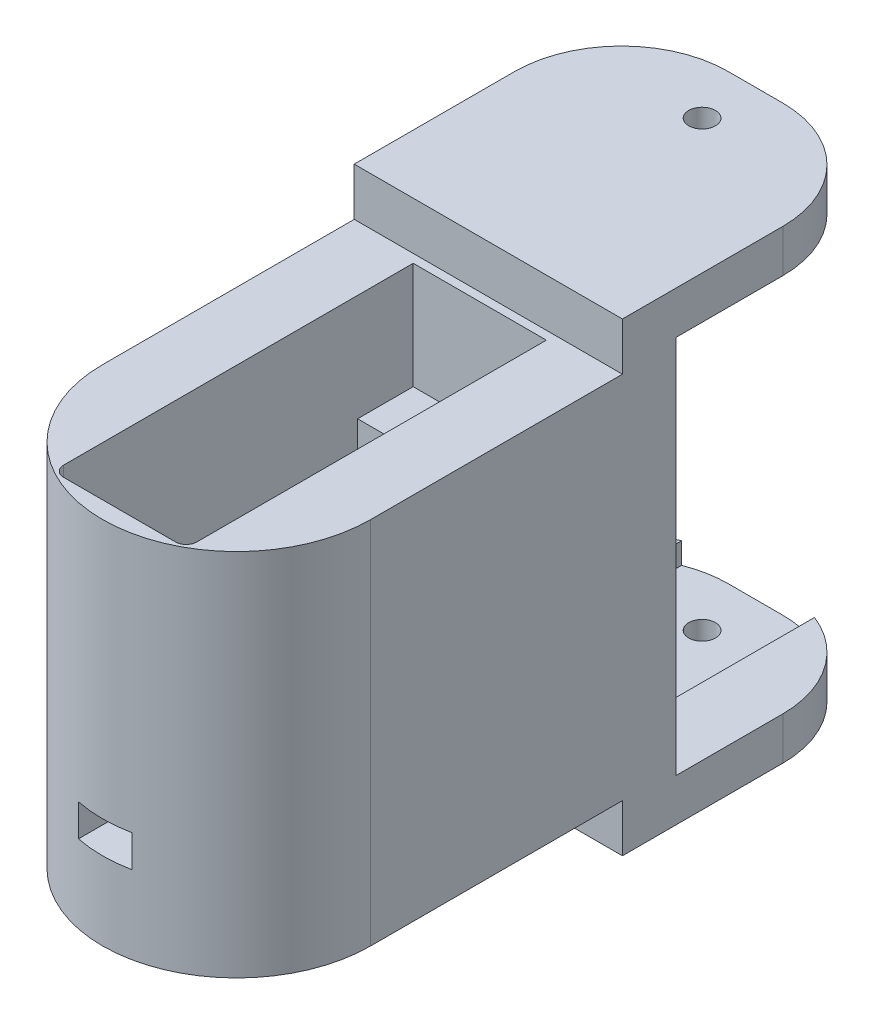
SolidWorks part; units mm, degrees
ref_plane "Front Plane" through (0, 0, 0) normal (0, 0, 1) x (1, 0, 0)
ref_plane "Top Plane" through (0, 0, 0) normal (0, 1, 0) x (1, 0, 0)
ref_plane "Right Plane" through (0, 0, 0) normal (1, 0, 0) x (0, 0, -1)
sketch "Sketch4" plane through (0, 0, 0) normal (0, 0, 1) x (1, 0, 0)
  line L1 (-6.23, -9.975) -> (6.23, -9.975)
  line L2 (-6.23, -9.975) -> (-6.23, 7.275)
  line L3 (-6.23, 7.275) -> (6.23, 7.275)
  line L4 (6.23, -9.975) -> (6.23, 7.275)
  point P4 (0, 7.275)
  dimension "D1" = 12.46
  dimension "D2" = 17.25
  dimension "D3" = 9.975
extrude "Boss-Extrude3" add sketch "Sketch4" along normal blind 6
sketch "Sketch8" plane through (0, -9.975, 0) normal (0, -1, 0) x (-1, 0, 0)
  circle A0 centre (0, -23.55) radius 12.5468
  circle A1 centre (0, -23.55) radius 11.15
  dimension "D1" = 22.3
  dimension "D2" = 23.55
extrude "Boss-Extrude6" add sketch "Sketch8" along normal blind 7.3 and the other way up to surface (17.25 mm away) other way up to face at (0, 7.275, 3)
sketch "Sketch5" plane through (0, 7.275, 0) normal (0, 1, 0) x (1, 0, 0)
  line L8 (12.5468, -23.55) -> (12.5468, 0)
  line L9 (12.5468, 0) -> (6.23, 0)
  line L10 (-12.5468, -23.55) -> (-12.5468, 0)
  line L11 (-12.5468, 0) -> (-6.23, 0)
  line L12 (-6.23, 0) -> (-6.23, -29.7)
  line L14 (6.23, -29.7) -> (6.23, 0)
  line L15 (-6.23, -29.7) -> (6.23, -29.7)
  line L16 (6.23, -6) -> (-6.23, -6) construction
  circle A0 centre (0, -23.55) radius 12.5468 construction
  arc A1 (-12.5468, -23.55) -> (12.5468, -23.55) centre (0, -23.55) ccw
  dimension "D1" = 23.7
  dimension "D2" = 23.55
extrude "Boss-Extrude4" add sketch "Sketch5" against normal up to surface (17.25 mm away) up to face at (0, -9.975, 3)
sketch "Sketch6" plane through (0, 7.275, 0) normal (0, 1, 0) x (1, 0, 0)
  line L0 (6.23, -6) -> (-6.23, -6) construction
  line L3 (6.23, -29.7) -> (-6.23, -29.7) construction
  circle A0 centre (0, -3.6) radius 0.5
  circle A1 centre (0, -32.1) radius 0.5
  dimension "D1" = 1
  dimension "D3" = 1
  dimension "D2" = 2.4
  dimension "D4" = 2.4
extrude "Cut-Extrude1" cut sketch "Sketch6" against normal blind 5
chamfer "Chamfer1" distance 0.5 angle 60 2 edges at (0, 7.275, 4.1) (0, 7.275, 32.6) first distance on face at (0, 7.275, 4.1)
sketch "Sketch10" plane through (0, 7.275, 0) normal (0, 1, 0) x (1, 0, 0)
  line L1 (-6.23, -6) -> (6.23, -6)
  line L2 (-6.23, -6) -> (-6.23, -29.7)
  line L3 (-6.23, -29.7) -> (6.23, -29.7)
  line L4 (6.23, -6) -> (6.23, -29.7)
extrude "Cut-Extrude3" cut sketch "Sketch10" against normal up to surface (17.25 mm away) up to face at (0, -9.975, 27.1007)
ref_plane "Plane1" through (0, 0, 36.0968) normal (0, 0, 1) x (1, 0, 0)
sketch "Sketch11" plane through (0, 0, 36.0968) normal (0, 0, 1) x (1, 0, 0)
  line L0 (-11.15, -9.975) -> (11.15, -9.975) construction
  line L1 (-2.5, -6.975) -> (2.5, -6.975)
  line L2 (-2.5, -6.975) -> (-2.5, -9.975)
  line L3 (-2.5, -9.975) -> (2.5, -9.975)
  line L4 (2.5, -6.975) -> (2.5, -9.975)
  point P4 (0, -6.975)
  dimension "D1" = 0
  dimension "D2" = 5
  dimension "D3" = 3
extrude "Cut-Extrude4" cut sketch "Sketch11" against normal up to next
sketch "Sketch13" plane through (0, -17.275, 0) normal (0, -1, 0) x (1, 0, 0)
  line L0 (-12.5468, 23.55) -> (-12.5468, 0)
  line L1 (-12.5468, 0) -> (12.5468, 0)
  line L2 (12.5468, 0) -> (12.5468, 23.55)
  arc A0 (-12.5468, 23.55) -> (12.5468, 23.55) centre (0, 23.55) ccw
  point P3 (0, 0)
extrude "Boss-Extrude7" add sketch "Sketch13" against normal up to surface (7.3 mm away) up to face at (6.0145, -9.975, 27.3356)
sketch "Sketch15" plane through (0, 7.275, 0) normal (0, 1, 0) x (1, 0, 0)
  line L0 (-12.5468, 0) -> (12.5468, 0)
  line L1 (12.5468, 0) -> (12.5468, -23.55)
  line L2 (-12.5468, 0) -> (-12.5468, -23.55)
  line L3 (6.23, -6) -> (6.23, -29.7) construction
  line L4 (-6.23, -0.8) -> (6.23, -0.8)
  line L5 (-6.23, -0.8) -> (-6.23, -33.5)
  line L6 (-5.23, -34.5) -> (5.23, -34.5)
  line L7 (6.23, -0.8) -> (6.23, -33.5)
  arc A0 (-12.5468, -23.55) -> (12.5468, -23.55) centre (0, -23.55) ccw
  circle A1 centre (0, -3.6) radius 0.5 construction
  arc A2 (5.23, -34.5) -> (6.23, -33.5) centre (5.23, -33.5) ccw
  arc A3 (-6.23, -33.5) -> (-5.23, -34.5) centre (-5.23, -33.5) ccw
  point P15 (0, -0.8)
  dimension "D1" = 0.8
  dimension "D3" = 1
  dimension "D2" = 2.8
  dimension "D4" = 0
  dimension "D5" = 34.5
extrude "Boss-Extrude9" add sketch "Sketch15" along normal blind 10
sketch "Sketch20" plane through (0, -17.275, 0) normal (0, -1, 0) x (1, 0, 0)
  circle A0 centre (0, 23.55) radius 7.15
  circle A1 centre (0, 23.55) radius 11.15
  circle A2 centre (0, 23.55) radius 11.15 construction
  dimension "D1" = 14.3
extrude "Boss-Extrude11" add sketch "Sketch20" against normal up to surface (7.3 mm away) up to face at (-6.0145, -9.975, 27.3356)
sketch "Sketch17" plane through (-12.5468, 4.7282, 0) normal (1, 0, 0) x (0, -1, 0)
  line L0 (26.4782, 25) -> (26.4782, 0)
  line L1 (26.4782, 0) -> (-17.0218, 0)
  line L2 (-17.0218, 0) -> (-17.0218, 25)
  line L3 (-17.0218, 25) -> (-13.0218, 25)
  line L4 (-13.0218, 25) -> (-13.0218, 5)
  line L5 (-13.0218, 5) -> (22.4782, 5)
  line L6 (22.4782, 5) -> (22.4782, 25)
  line L7 (22.4782, 25) -> (26.4782, 25)
  point P2 (4.7282, 5)
  point P10 (4.7282, 0)
  dimension "D1" = 4
  dimension "D2" = 35.5
  dimension "D3" = 0
  dimension "D4" = 25
  dimension "D5" = 5
extrude "Boss-Extrude10" add sketch "Sketch17" along normal up to surface (25.0936 mm away) up to face at (12.5468, 0, 11.775)
sketch "Sketch18" plane through (0, -17.75, 0) normal (0, 1, 0) x (0, 0, 1)
  line L0 (-25, -12.5468) -> (-25, 12.5468) construction
  line L1 (-25, 6.2191) -> (-5, 6.2191)
  line L2 (-25, 6.2191) -> (-25, -6.2191)
  line L3 (-25, -6.2191) -> (-5, -6.2191)
  line L4 (-5, 6.2191) -> (-5, -6.2191)
  line L5 (-5, -12.5468) -> (-5, 12.5468) construction
  point P6 (-25, 0)
  point P7 (-25, 0)
  dimension "D1" = 0
extrude "Cut-Extrude5" cut sketch "Sketch18" against normal blind 2
sketch "Sketch19" plane through (0, -19.75, 0) normal (0, 1, 0) x (0, 0, 1)
  line L0 (-25, -12.5468) -> (-25, 12.5468) construction
  circle A0 centre (-20, 0) radius 1.25
  dimension "D1" = 2.5
  dimension "D2" = 5
extrude "Cut-Extrude6" cut sketch "Sketch19" against normal through all both and the other way through all
fillet "Fillet1" radius 10 4 edges at (12.5468, -19.75, -25) (-12.5468, -19.75, -25) (-12.5468, 19.75, -25) (12.5468, 19.75, -25)
ref_plane "Plane2" through (0, 0, 0) normal (1, 0, 0) x (0, 0, -1)
ref_plane "Plane3" through (0, 0, 0) normal (0, -1, 0) x (-1, 0, 0)
sketch "Sketch21" plane through (0, -17.275, 0) normal (0, -1, 0) x (1, 0, 0)
  circle A0 centre (0, 23.55) radius 7.15
  circle A1 centre (0, 23.55) radius 10.15
  circle A2 centre (0, 23.55) radius 7.15 construction
  dimension "D1" = 20.3
extrude "Cut-Extrude7" cut sketch "Sketch21" against normal blind 1.8
